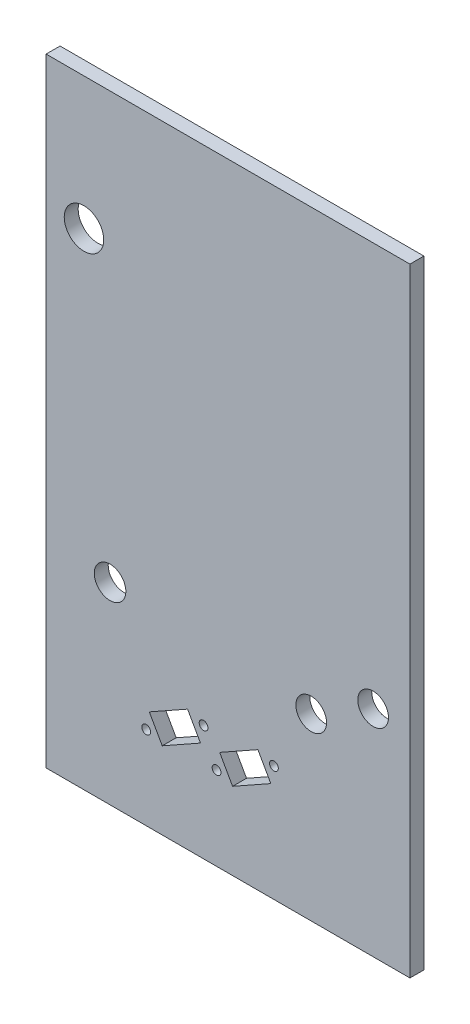
SolidWorks part; units mm, degrees
ref_plane "Front Plane" through (0, 0, 0) normal (0, 0, 1) x (1, 0, 0)
ref_plane "Top Plane" through (0, 0, 0) normal (0, 1, 0) x (1, 0, 0)
ref_plane "Right Plane" through (0, 0, 0) normal (1, 0, 0) x (0, 0, -1)
sketch "Sketch1" plane through (0, 0, 0) normal (0, 0, 1) x (1, 0, 0)
  line L0 (-0.0069, 73.6677) -> (0.001, 62.5277) construction
  line L1 (0.001, 62.5277) -> (0.001, 56.2377) construction
  line L2 (0.001, 56.2377) -> (0.001, 10.269) construction
  line L3 (-15.5819, -49.7766) -> (-8.6537, -45.7766) construction
  line L4 (-15.5819, -49.7766) -> (0.4181, -49.7766) construction
  line L5 (0.4181, -49.7766) -> (7.4146, -45.7372) construction
  line L6 (0.001, 10.269) -> (-0.0069, -73.6266) construction
  line L7 (-18.6546, -51.4536) -> (-5.581, -44.0996) construction
  line L8 (-15.0049, -52.8426) -> (-6.2892, -47.94)
  line L9 (-15.0049, -52.8426) -> (-17.9465, -47.6132)
  line L14 (-17.9465, -47.6132) -> (-9.2307, -42.7106)
  line L15 (-16.3293, -29.1587) -> (-16.3293, -23.8757)
  line L16 (-6.2892, -47.94) -> (-9.2307, -42.7106)
  line L17 (-15.0049, -52.8426) -> (-9.2307, -42.7106) construction
  line L18 (-17.9465, -47.6132) -> (-6.2892, -47.94) construction
  line L19 (1.0292, -52.8229) -> (9.745, -47.9203)
  line L20 (-0.4459, -48.2227) -> (6.5873, -44.2665) construction
  line L21 (8.2583, -47.1985) -> (1.3584, -51.2855) construction
  line L22 (-44.6519, 73.6677) -> (44.6381, 73.6677)
  line L23 (44.6381, 73.6677) -> (44.6381, -73.6266)
  line L24 (44.6381, -73.6266) -> (-44.6519, -73.6266)
  line L25 (-44.6519, -73.6266) -> (-44.6519, 73.6677)
  line L26 (-25.0598, 56.2377) -> (-25.0598, 10.2698)
  line L27 (-25.0598, 10.2698) -> (25.0617, 10.2682)
  line L28 (25.0617, 10.2682) -> (25.0617, 56.2377)
  line L29 (25.0617, 56.2377) -> (-25.0598, 56.2377)
  line L30 (9.745, -47.9203) -> (6.8034, -42.6909)
  line L31 (1.0292, -52.8229) -> (-1.9123, -47.5935)
  line L32 (-1.9123, -47.5935) -> (6.8034, -42.6909)
  line L33 (-2.6205, -51.4338) -> (10.4531, -44.0799) construction
  line L34 (35.9211, 62.5277) -> (-35.9192, 62.5277)
  line L35 (-38.5319, 59.99) -> (-38.5319, 6.918)
  line L36 (-35.9293, 4.4201) -> (29.9974, 4.418)
  line L37 (38.3896, 13.668) -> (38.3865, 59.8943)
  line L38 (-16.4095, -48.3053) -> (-9.4374, -44.3835) construction
  line L39 (-7.8545, -47.1609) -> (-14.7543, -51.2479) construction
  line L150 (42.2525, -55.0539) -> (42.2511, -54.9499)
  circle A1 centre (-18.6546, -51.4536) radius 1
  circle A2 centre (-26.9008, -26.5172) radius 3.6
  arc A3 (8.2583, -47.1985) -> (6.5873, -44.2665) centre (7.4146, -45.7372) ccw construction
  circle A4 centre (-5.581, -44.0996) radius 1
  circle A5 centre (-2.6205, -51.4338) radius 1
  arc A6 (-16.4095, -48.3053) -> (-14.7543, -51.2479) centre (-15.5819, -49.7766) ccw construction
  arc A7 (-7.8545, -47.1609) -> (-9.4374, -44.3835) centre (-8.6537, -45.7766) ccw construction
  circle A12 centre (10.4531, -44.0799) radius 1
  circle A15 centre (18.9576, -29.5613) radius 3.5
  circle A16 centre (33.0683, -21.4917) radius 3.5
  arc A17 (-0.4459, -48.2227) -> (1.3584, -51.2855) centre (0.4181, -49.7766) ccw construction
  circle A19 centre (-32.8459, 40.3636) radius 4.5
  arc A24 (38.3865, 59.8943) -> (35.9211, 62.5277) centre (35.8901, 60.0279) ccw
  arc A25 (-35.9192, 62.5277) -> (-38.5319, 59.99) centre (-35.9192, 59.9138) ccw
  arc A26 (-38.5319, 6.918) -> (-35.9293, 4.4201) centre (-36.0319, 6.918) ccw
  arc A27 (29.9974, 4.418) -> (38.3896, 13.668) centre (29.1397, 13.6282) ccw
  point P5 (-12.1178, -47.7766)
  point P51 (-12.1178, -47.7766)
  point P64 (3.9163, -47.7569)
  dimension "D4" = 11.14
  dimension "D8" = 7
  dimension "D11" = 9
  dimension "D12" = 7.2
  dimension "D14" = 9.25
  dimension "D15" = 2.5
  dimension "D27" = 2
  dimension "D2" = 89.29
  dimension "D3" = 147.2943
  dimension "D5" = 25.9097
  dimension "D6" = 8.0696
  dimension "D7" = 14.1107
  dimension "D9" = 7.7861
  dimension "D10" = 22.1641
  dimension "D13" = 10.5715
  dimension "D16" = 6.29
  dimension "D17" = 6.12
  dimension "D18" = 5.85
  dimension "D19" = 16
  dimension "D20" = 8
  dimension "D21" = 29.07
  dimension "D22" = 23.85
  dimension "D23" = 30
  dimension "D24" = 6
  dimension "D25" = 10
  dimension "D26" = 15
extrude "Bezel" add sketch "Sketch1<6>" along normal blind 3.18 contours L36 A27 L37 A24 L34 A25 L35 A26 L29 L28 L27 L26 A19 region at (37.0114, 61.0776, 0)
sketch "Sketch1<6>" plane through (0, 0, 0) normal (0, 0, 1) x (1, 0, 0) same geometry as "Sketch1"
extrude "Body" add sketch "Sketch1" along normal blind 3.18 contours L25 L24 L23 L22 A27 L36 A26 L35 A25 L34 A24 L37 A17 L20 A3 L21 A16 A15 A7 L39 A6 L38 A2 region at (0.055, -16.5213, 0)
extrude "Boss-Extrude1" add sketch "Sketch1<11>" along normal blind 3.18 contours L28 L29 L26 L27 region at (0.0011, 33.2533, 0)
sketch "Sketch1<11>" plane through (0, 0, 0) normal (0, 0, 1) x (1, 0, 0) same geometry as "Sketch1"
sketch "Sketch2" plane through (0, 0, 3.18) normal (0, 0, 1) x (1, 0, 0)
  line L0 (-41.4719, 70.4877) -> (-41.4719, -70.4466)
  line L1 (-41.4719, -70.4466) -> (41.4581, -70.4466)
  line L2 (41.4581, -70.4466) -> (41.4581, 70.4877)
  line L3 (41.4581, 70.4877) -> (-41.4719, 70.4877)
  line L4 (-44.6519, 73.6677) -> (-44.6519, -73.6266)
  line L5 (-44.6519, -73.6266) -> (44.6381, -73.6266)
  line L6 (44.6381, -73.6266) -> (44.6381, 73.6677)
  line L7 (44.6381, 73.6677) -> (-44.6519, 73.6677)
  line L8 (-44.6519, 73.6677) -> (-44.6519, -73.6266)
  line L9 (-44.6519, -73.6266) -> (44.6381, -73.6266)
  line L10 (44.6381, -73.6266) -> (44.6381, 73.6677)
  line L11 (44.6381, 73.6677) -> (-44.6519, 73.6677)
  dimension "D1" = 0
  dimension "D2" = 3.18
extrude "Cut-Extrude1" cut sketch "Sketch2" against normal through all
